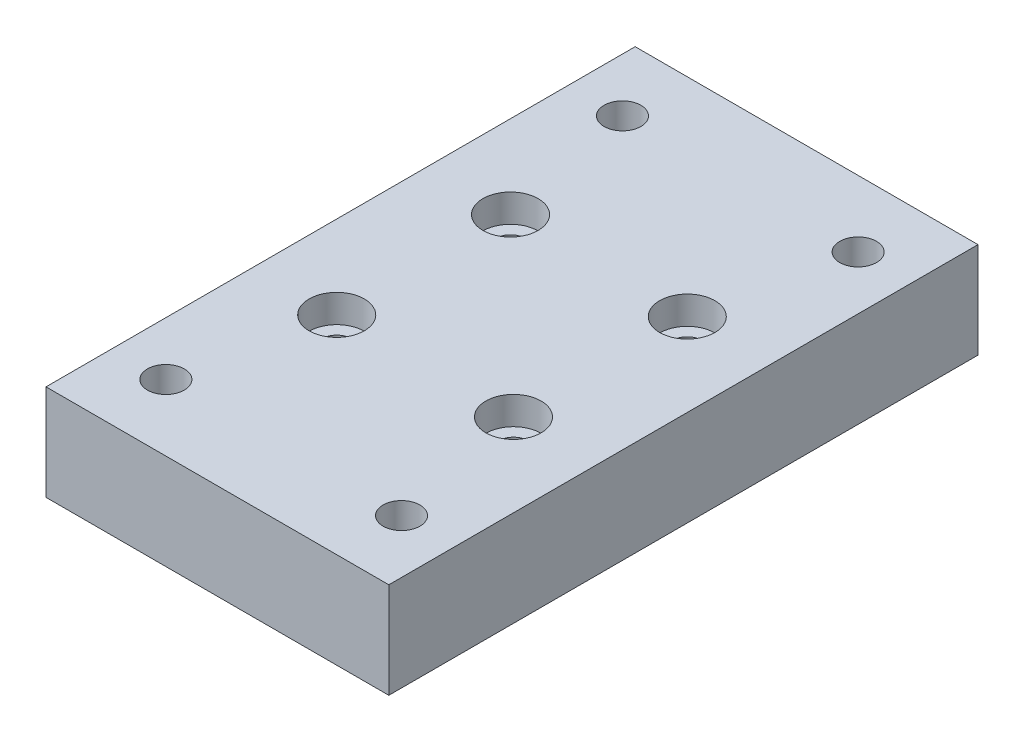
SolidWorks part; units mm, degrees
material "6061-T6 (SS)"
ref_plane "Front Plane" through (0, 0, 0) normal (0, 0, 1) x (1, 0, 0)
ref_plane "Top Plane" through (0, 0, 0) normal (0, 1, 0) x (1, 0, 0)
ref_plane "Right Plane" through (0, 0, 0) normal (1, 0, 0) x (0, 0, -1)
sketch "Sketch1" plane through (0, 0, 0) normal (0, 1, 0) x (1, 0, 0)
  line L1 (-29.5593, -50.8) -> (29.5593, -50.8)
  line L2 (-29.5593, -50.8) -> (-29.5593, 50.8)
  line L3 (-29.5593, 50.8) -> (29.5593, 50.8)
  line L4 (29.5593, -50.8) -> (29.5593, 50.8)
  line L5 (-29.5593, -50.8) -> (29.5593, 50.8) construction
  line L6 (-29.5593, 50.8) -> (29.5593, -50.8) construction
  point P0 (0, 0)
  dimension "D1" = 101.6
  dimension "D2" = 59.1185
extrude "Boss-Extrude1" add sketch "Sketch1" along normal blind 16.51
hole_wizard "CBORE for #10 Socket Head Cap Screw1" positions "Sketch2" profile "Sketch3" counterbore size "#10" standard "ANSI Inch"
sketch "Sketch2" plane through (-145.6753, 16.51, 0) normal (0, 1, 0) x (0, 0, 1)
  point P0 (-14.986, 130.4353)
  point P1 (14.986, 130.4353)
  point P2 (14.986, 160.9153)
  point P3 (-14.986, 160.9153)
sketch "Sketch3" plane through (-15.24, 16.51, -14.986) normal (1, 0, 0) x (0, 0, 1)
  line L0 (0, 0) -> (0, 15.24)
  line L1 (0, 15.24) -> (2.5527, 15.24)
  line L2 (2.5527, 15.24) -> (2.5527, 4.826)
  line L3 (2.5527, 4.826) -> (4.7625, 4.826)
  line L4 (4.7625, 4.826) -> (4.7625, 0)
  line L5 (4.7625, 0) -> (0, 0)
  line L6 (0, -6.35) -> (0, 107.95) construction
  dimension "Thru Hole Dia." = 5.1054
  dimension "Thru Hole Depth" = 15.24
  dimension "C'Bore Dia." = 9.525
  dimension "C'Bore Depth" = 4.826
hole_wizard "1/4 (0.25) Diameter Hole1" positions "Sketch4" profile "Sketch5" hole size "1/4" standard "ANSI Inch" end condition through all
sketch "Sketch4" plane through (0, 16.51, 0) normal (0, 1, 0) x (1, 0, 0)
  line L0 (20.32, 39.37) -> (20.32, -39.37) construction
  line L3 (29.5593, -50.8) -> (29.5593, 50.8) construction
  line L4 (20.32, 39.37) -> (-20.32, 39.37) construction
  line L6 (29.5593, 50.8) -> (-29.5593, 50.8) construction
  point P0 (20.32, -39.37)
  point P2 (-20.32, -39.37)
  point P4 (-20.32, 39.37)
  point P6 (20.32, 39.37)
  point P16 (20.32, 0)
  point P19 (29.5593, 0)
  point P25 (0, 39.37)
  point P28 (0, 50.8)
  point P29 (0, 0)
  point P30 (0, 0)
  dimension "D1" = 78.74
  dimension "D2" = 40.64
sketch "Sketch5" plane through (20.32, 16.51, 39.37) normal (1, 0, 0) x (0, 0, 1)
  line L0 (0, 0) -> (0, 16.51)
  line L1 (0, 16.51) -> (3.175, 16.51)
  line L2 (3.175, 16.51) -> (3.175, 0)
  line L5 (3.175, 0) -> (0, 0)
  line L11 (0, -6.35) -> (0, 107.95) construction
  dimension "Thru Hole Dia." = 6.35
  dimension "Thru Hole Depth" = 16.51
